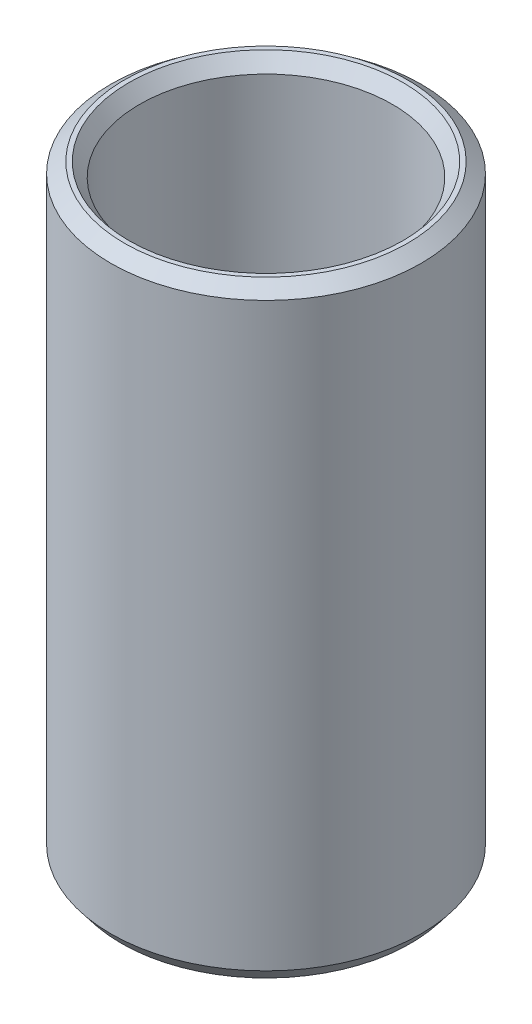
SolidWorks part; units mm, degrees
ref_plane "Front Plane" through (0, 0, 0) normal (0, 0, 1) x (1, 0, 0)
ref_plane "Top Plane" through (0, 0, 0) normal (0, 1, 0) x (1, 0, 0)
ref_plane "Right Plane" through (0, 0, 0) normal (1, 0, 0) x (0, 0, -1)
sketch "Sketch1" plane through (0, 0, 0) normal (0, 1, 0) x (1, 0, 0)
  circle A0 centre (0, 0) radius 45
  dimension "SLEEVE_OD" = 90
extrude "Boss-Extrude1" add sketch "Sketch1" along normal blind 175.3677
sketch "Sketch2" plane through (0, 0, 0) normal (0, 1, 0) x (1, 0, 0)
  circle A0 centre (0, 0) radius 36.6696
  dimension "BORE_D" = 73.3392
extrude "Cut-Extrude1" cut sketch "Sketch2" along normal through all
chamfer "Chamfer1" distance 3.0564 angle 52.279 4 edges at (0, 175.3677, 36.6696) (0, 0, 36.6696) (0, 0, 45) (0, 175.3677, 45) first distance on face at (0, 175.3677, 36.6696) first distance on face at (0, 0, 36.6696) first distance on face at (0, 175.3677, 45)
